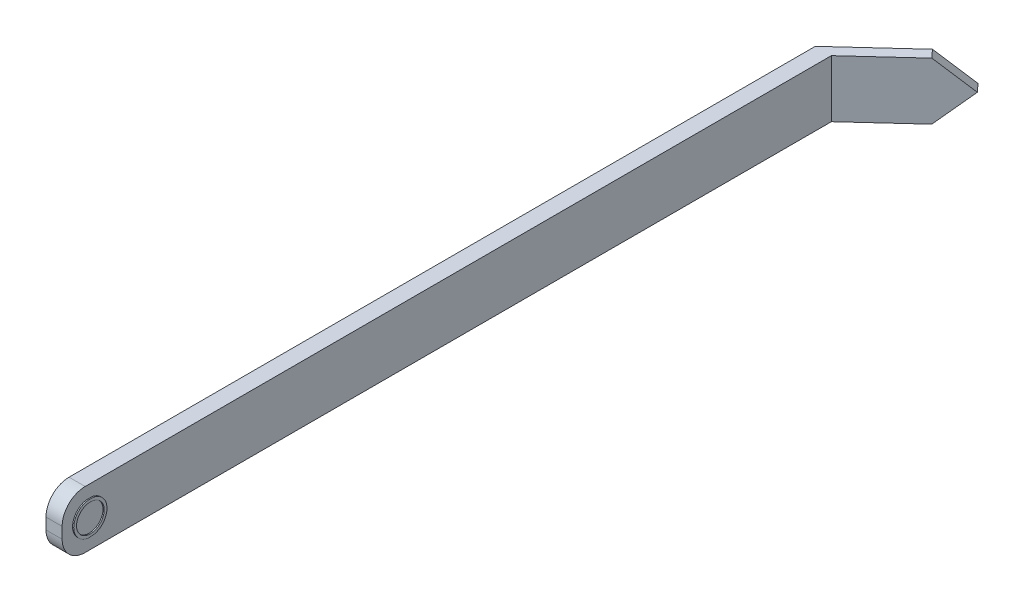
SolidWorks part; units mm, degrees
note: The reader was unsure of these and kept them because the rebuilt part matched: shared geometry of "Sketch7<3>", "Sketch7<5>", "Sketch1<4>".
material "Custom Plastic"
ref_plane "Front Plane" through (0, 0, 0) normal (0, 0, 1) x (1, 0, 0)
ref_plane "Top Plane" through (0, 0, 0) normal (0, 1, 0) x (1, 0, 0)
ref_plane "Right Plane" through (0, 0, 0) normal (1, 0, 0) x (0, 0, -1)
sketch "Sketch1" plane through (0, 0, 0) normal (1, 0, 0) x (0, 0, -1)
  line L1 (0, 0) -> (167, 0)
  line L2 (0, 0) -> (0, 12.42)
  line L3 (0, 12.42) -> (167, 12.42)
  line L6 (167, 0) -> (167, 12.42)
  line L7 (167, 12.42) -> (180, 12.42)
  line L8 (180, 12.42) -> (187, 6.21)
  line L9 (187, 6.21) -> (180, 0)
  line L10 (180, 0) -> (167, 0)
  point P6 (167, 6.21)
  dimension "D1" = 13
  dimension "D2" = 12.42
  dimension "D3" = 167
  dimension "D4" = 20
extrude "Boss-Extrude1" add sketch "Sketch1" along normal blind 3.5 contours L1 L6 L3 L2 | L10 L9 L8 L7 L6
sketch "Sketch7" plane through (0, 0, 0) normal (-1, 0, 0) x (0, 0, 1)
  line L0 (-5.4156, 9.79) -> (-23.4102, 8.715)
  line L1 (-23.4102, 3.705) -> (-5.4156, 2.63)
  line L2 (0, 0) -> (0, 12.42) construction
  line L3 (0, 12.42) -> (-180, 12.42) construction
  line L4 (-160, 0) -> (-160, 12.42) construction
  line L5 (0, 0) -> (-180, 0) construction
  circle A0 centre (-5.88, 6.21) radius 3.61
  arc A1 (-23.4102, 8.715) -> (-23.4102, 3.705) centre (-23.2605, 6.21) ccw
  circle A2 centre (-5.88, 6.21) radius 3
  point P6 (0, 6.21)
  point P8 (-5.88, 6.21)
  dimension "D1" = 7.22
  dimension "D4" = 23.5
  dimension "D5" = 5.01
  dimension "D7" = 6
  dimension "D2" = 7.16
  dimension "D3" = 5.88
  dimension "D6" = 20
extrude "Cut-Extrude1" cut sketch "Sketch7" against normal through all contours A0
extrude "Cut-Extrude2" cut sketch "Sketch7<3>" against normal offset from surface (1.8 mm away) 1.7 contours L0 A1 L1 A0 up to face at (3.5, 6.21, -5.9857)
sketch "Sketch7<3>" plane through (0, 0, 0) normal (-1, 0, 0) x (0, 0, 1) same geometry as "Sketch7"
fillet "Fillet1" radius 5 2 edges at (1.75, 12.42, 0) (1.75, 0, 0)
fillet "Fillet2" radius 2 2 edges at (2.65, 2.7108, -6.7673) (2.65, 9.7092, -6.7673)
ref_plane "Plane1" through (0, 8.715, -23.4102) normal (0, -0.0596, -0.9982) x (-1, 0, 0)
extrude "Boss-Extrude2" add sketch "Sketch7<5>" along normal blind 0.25 from surface at -3.5 separate body contours L0 A0 L1 A2
sketch "Sketch7<5>" plane through (0, 0, 0) normal (-1, 0, 0) x (0, 0, 1) same geometry as "Sketch7"
extrude "Cut-Extrude5" cut sketch "Sketch1<4>" against normal through all both and the other way through all contours L10 L9 L8 L7 L6
sketch "Sketch1<4>" plane through (0, 0, 0) normal (1, 0, 0) x (0, 0, -1) same geometry as "Sketch1"
sketch "Sketch8" plane through (0, 12.42, 0) normal (0, 1, 0) x (1, 0, 0)
  line L0 (3.5, 167) -> (20.0247, 182.1527)
  line L1 (20.0247, 182.1527) -> (18.426, 183.8962)
  line L2 (18.426, 183.8962) -> (0, 167)
  line L4 (0, 167) -> (-12.4299, 167) construction
  line L9 (3.5, 5) -> (3.5, 167)
  line L10 (3.5, 167) -> (0, 167)
  line L11 (0, 167) -> (0, 5)
  line L12 (0, 5) -> (3.5, 5)
  line L14 (3.5, 167) -> (0, 167)
  dimension "D1" = 137.48
  dimension "D2" = 25
  dimension "D3" = 0
extrude "Boss-Extrude3" add sketch "Sketch8" against normal blind 12.42
sketch "Sketch9" plane through (-83.1873, 0, -90.7194) normal (-0.6758, 0, -0.737) x (-0.737, 0, 0.6758)
  line L0 (-137.8665, 6.21) -> (-130.8665, 12.42)
  line L1 (-137.8665, 0) -> (-137.8665, 12.42) construction
  line L2 (-137.8665, 12.42) -> (-112.8665, 12.42) construction
  line L3 (-130.8665, 12.42) -> (-130.8665, 0)
  line L4 (-137.8665, 0) -> (-112.8665, 0) construction
  line L5 (-130.8665, 0) -> (-137.8665, 6.21)
  line M4 (-112.8665, 12.42) -> (-137.8665, 12.42)
  line M5 (-137.8665, 12.42) -> (-137.8665, 0)
  line M6 (-137.8665, 0) -> (-112.8665, 0)
  dimension "D1" = 7
extrude "Cut-Extrude7" cut sketch "Sketch9" against normal through all both and the other way through all contours L0 M5 M4 | L5 M6 M5
